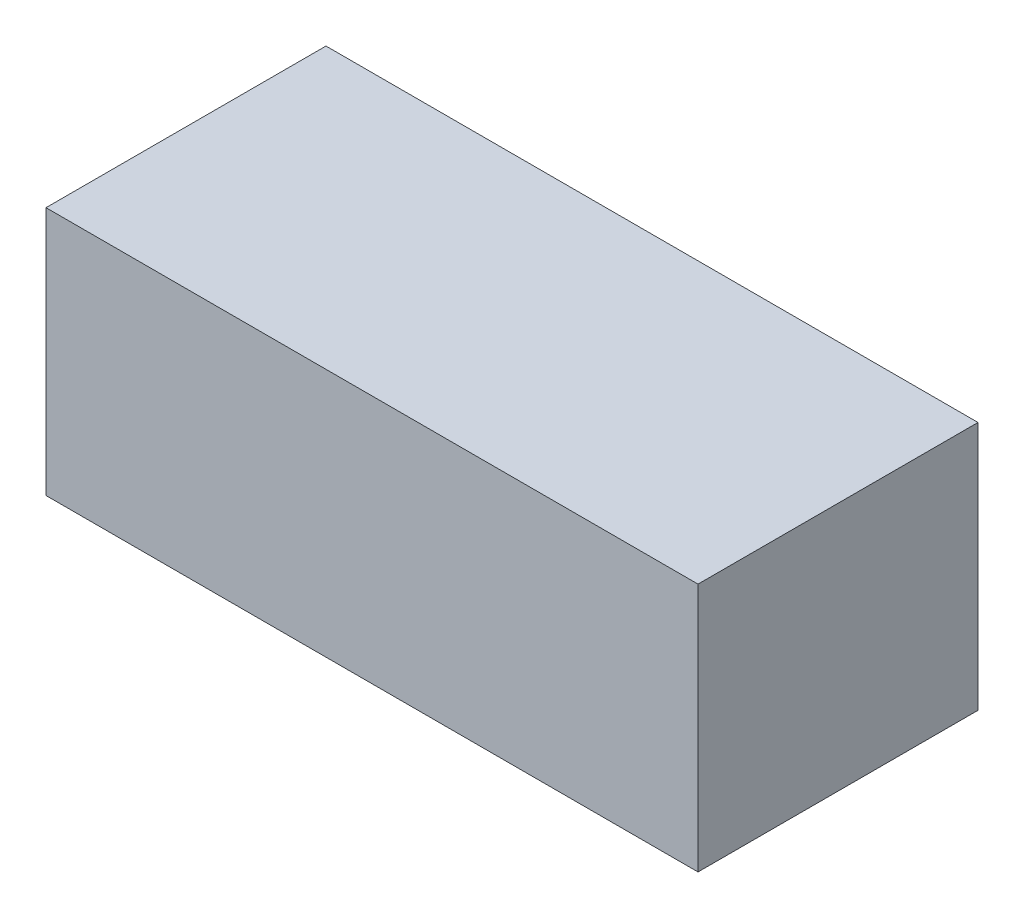
SolidWorks part; units mm, degrees
ref_plane "XY" through (0, 0, 0) normal (0, 0, 1) x (1, 0, 0)
ref_plane "XZ" through (0, 0, 0) normal (0, 1, 0) x (1, 0, 0)
ref_plane "YZ" through (0, 0, 0) normal (1, 0, 0) x (0, 0, -1)
ref_axis "X" through (-23.749, 0, 0) along (1, 0, 0)
ref_axis "Y" through (0, -0.75, 0) along (0, 1, 0)
ref_axis "Z" through (0, 0, 10.1981) along (0, 0, -1)
sketch "Sketch1" plane through (0, 0, 0) normal (0, 1, 0) x (1, 0, 0)
  line L1 (-21.59, -9.271) -> (21.59, -9.271)
  line L2 (-21.59, -9.271) -> (-21.59, 9.271)
  line L3 (-21.59, 9.271) -> (21.59, 9.271)
  line L4 (21.59, -9.271) -> (21.59, 9.271)
  line L5 (-21.59, -9.271) -> (21.59, 9.271) construction
  line L6 (-21.59, 9.271) -> (21.59, -9.271) construction
  point P0 (0, 0)
  dimension "D1" = 43.18
  dimension "D2" = 18.542
extrude "Boss-Extrude1" add sketch "Sketch1" along normal blind 16.51
